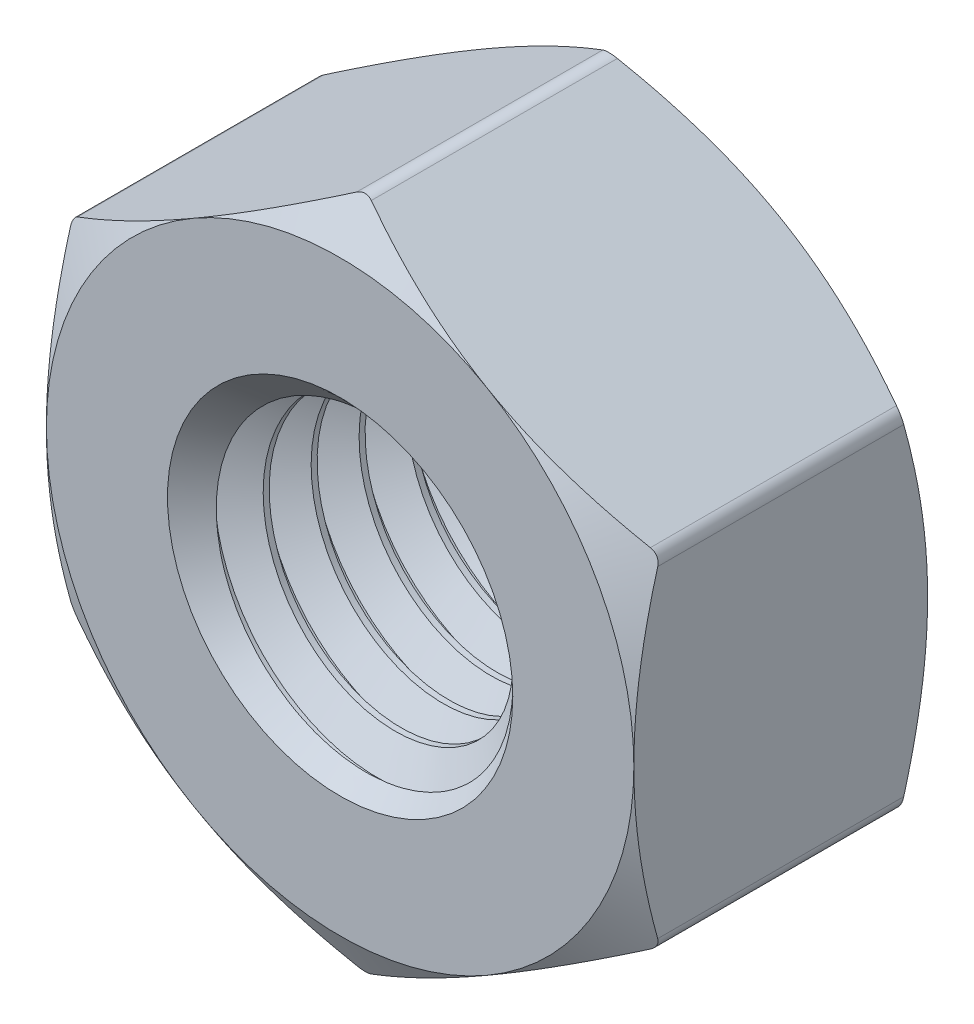
SolidWorks part; units mm, degrees
ref_plane "Front" through (0, 0, 0) normal (0, 0, 1) x (1, 0, 0)
ref_plane "Top" through (0, 0, 0) normal (0, 1, 0) x (1, 0, 0)
ref_plane "Right" through (0, 0, 0) normal (1, 0, 0) x (0, 0, -1)
sketch "Sketch1" plane through (0, 0, 0) normal (0, 0, 1) x (1, 0, 0)
  line L0 (0, 3.175) -> (0, 2.2679) construction
  line L1 (-5.5563, 3.2079) -> (-5.5562, -3.2079)
  line L2 (-5.5562, -3.2079) -> (0, -6.4158)
  line L3 (0, -6.4158) -> (5.5562, -3.2079)
  line L4 (5.5562, -3.2079) -> (5.5562, 3.2079)
  line L5 (5.5562, 3.2079) -> (0, 6.4158)
  line L6 (0, 6.4158) -> (-5.5563, 3.2079)
  circle A0 centre (0, 0) radius 5.5562 construction
  circle A1 centre (0, 0) radius 3.175 construction
  point P10 (0, 3.175)
  dimension "Width" = 11.1125
  dimension "Thread Size" = 6.35
  dimension "Thread Pitch" = 0.9071
sketch "Sketch2" plane through (0, 0, 0) normal (1, 0, 0) x (0, 0, -1)
  line L0 (-2.7781, 0) -> (2.7781, 0) construction
  line L1 (-2.7781, 6.4158) -> (2.7781, 6.4158) construction
  dimension "Height" = 5.5562
sketch "Sketch15" plane through (0, 0, 0) normal (0, 0, 1) x (1, 0, 0)
  line L1 (0, 6.4158) -> (-5.5563, 3.2079)
  line L2 (-5.5563, 3.2079) -> (-5.5563, -3.2079)
  line L3 (-5.5563, -3.2079) -> (0, -6.4158)
  line L4 (0, -6.4158) -> (5.5563, -3.2079)
  line L5 (5.5563, -3.2079) -> (5.5563, 3.2079)
  line L6 (5.5563, 3.2079) -> (0, 6.4158)
  circle A0 centre (0, 0) radius 5.5563 construction
extrude "Boss-Extrude2" add sketch "Sketch15" along normal mid plane 5.5562
sketch "Sketch16" plane through (0, 0, 0) normal (0, 0, 1) x (1, 0, 0)
  circle A0 centre (0, 0) radius 3.175 construction
  circle A1 centre (0, 0) radius 3.175
sketch "Sketch4" plane through (0, 0, -2.7781) normal (0, 0, -1) x (-1, 0, 0)
  circle A0 centre (0, 0) radius 3.175 construction
  circle A1 centre (0, 0) radius 3.175
extrude "Cut-Extrude4" cut sketch "Sketch16" against normal through all both and the other way through all
sketch "Sketch7" plane through (0, 0, 2.7781) normal (0, 0, 1) x (1, 0, 0)
  circle A0 centre (0, 0) radius 5.5562 construction
  circle A1 centre (0, 0) radius 5.5562
extrude "Cut-Extrude5" cut sketch "Sketch7" against normal through all draft 60 flip side to cut
mirror "Mirror4" about plane through (0, 0, 0) normal (0, 0, 1) of "Cut-Extrude5"
fillet "Fillet2" radius 0.2778 6 edges at (-5.5563, 3.2079, 0) (-5.5563, -3.2079, 0) (0, -6.4158, 0) (5.5563, -3.2079, 0) (5.5563, 3.2079, 0) (0, 6.4158, 0)
sketch "Sketch8" plane through (0, 0, 2.7781) normal (0, 0, 1) x (1, 0, 0)
  line L0 (0.8218, -3.0668) -> (0, 0) construction
  line L2 (0, 3.175) -> (0, 2.2679) construction
  circle A0 centre (0, 0) radius 3.175 construction
  point P0 (0.8218, -3.0668)
  dimension "D1" = 15
sketch "Sketch13" plane through (0, 0, -2.7781) normal (0, 0, -1) x (-1, 0, 0)
  circle A0 centre (0, 0) radius 3.175 construction
  circle A1 centre (0, 0) radius 3.175
extrude "Boss-Extrude1" add sketch "Sketch13" against normal up to surface (5.5563 mm away) separate body up to face at (3.175, 0, 2.7781)
curve "Helix/Spiral3" pitch 0.9071 height 6.4634 radius 3.175 centre (0, 0, -2.7781) axis (0, 0, 1) start towards (0, 1, 0)
sketch "Sketch12" plane through (0, 0, 0) normal (1, 0, 0) x (0, 0, -1)
  line L0 (3.5719, 3.175) -> (2.7781, 3.175)
  line L1 (3.5719, 3.175) -> (3.2317, 2.5858)
  line L2 (3.2317, 2.5858) -> (3.1183, 2.5858)
  line L3 (3.1183, 2.5858) -> (2.7781, 3.175)
  line L4 (3.175, 2.5858) -> (3.175, 3.175) construction
  line L5 (2.9482, 2.8804) -> (3.4018, 2.8804) construction
  dimension "D1" = 60
  dimension "D2" = 0.1134
  dimension "D3" = 0.4536
sweep "Cut-Sweep1" cut profiles "Sketch12" path "Helix/Spiral3" align with end faces yes
sketch "Sketch17" plane through (0, 0, 2.7781) normal (0, 0, 1) x (1, 0, 0)
  circle A1 centre (0, 0) radius 3.175
  circle A2 centre (0, 0) radius 3.175
  dimension "D1" = 0
extrude "Boss-Extrude3" add sketch "Sketch17" against normal up to surface (5.5563 mm away) up to face at (3.175, 0, -2.7781)
combine bodies "Combine1" operation type subtract main body 127 bodies to subtract 118
sketch "Sketch10" plane through (0, 0, 2.7781) normal (0, 0, 1) x (1, 0, 0)
  circle A0 centre (0, 0) radius 3.175 construction
  circle A1 centre (0, 0) radius 3.175 construction
  circle A2 centre (0, 0) radius 3.2657
  dimension "D1" = 0.0907
extrude "Cut-Extrude2" cut sketch "Sketch10" against normal through all draft 45
sketch "Sketch11" plane through (0, 0, -2.7781) normal (0, 0, -1) x (-1, 0, 0)
  circle A1 centre (0, 0) radius 3.2657 construction
  circle A2 centre (0, 0) radius 3.2657
extrude "Cut-Extrude3" cut sketch "Sketch11" against normal through all draft 45
equation "\"D1\"= \"Height@Sketch2\""
equation "\"D3@Helix/Spiral3\"=\"Height@Sketch2\"+\"Thread Pitch@Sketch1\""
equation "\"D4@Helix/Spiral3\"=\"Thread Pitch@Sketch1\""
equation "\"D2@Sketch12\" = \"D4@Helix/Spiral3\"*.125"
equation "\"D3@Sketch12\" = \"D4@Helix/Spiral3\"*.50"
equation "\"D1@Boss-Extrude2\"=\"Height@Sketch2\""
equation "\"D1@Fillet2\"=\"Width@Sketch1\"*0.025"
equation "\"D1@Sketch10\"=\"Thread Pitch@Sketch1\"*0.1"
